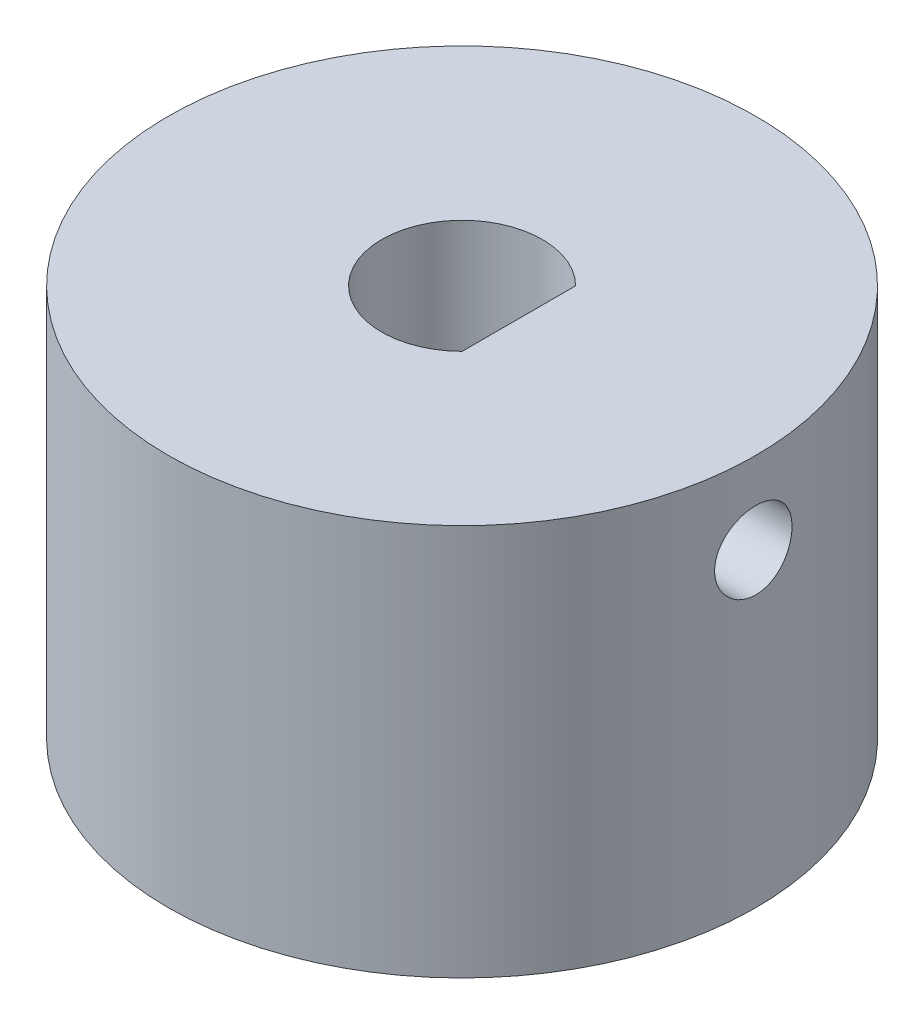
SolidWorks part; units mm, degrees
ref_plane "Front Plane" through (0, 0, 0) normal (0, 0, 1) x (1, 0, 0)
ref_plane "Top Plane" through (0, 0, 0) normal (0, 1, 0) x (1, 0, 0)
ref_plane "Right Plane" through (0, 0, 0) normal (1, 0, 0) x (0, 0, -1)
sketch "Sketch1" plane through (0, 0, 0) normal (0, 1, 0) x (1, 0, 0)
  circle A0 centre (0, 0) radius 9.525
  dimension "D1" = 19.05
extrude "Boss-Extrude1" add sketch "Sketch1" along normal mid plane 12.7
sketch "Sketch2" plane through (0, 6.35, 0) normal (0, 1, 0) x (1, 0, 0)
  line L0 (-2.6035, 4.0795) -> (-2.6035, -2.9289) construction
  line L1 (1.8415, 1.8404) -> (1.8415, -1.8404)
  arc A0 (1.8415, 1.8404) -> (1.8415, -1.8404) centre (0, 0) ccw
  dimension "D2" = 5.207
  dimension "D1" = 4.445
extrude "Cut-Extrude1" cut sketch "Sketch2" against normal up to surface (6.35 mm away) up to plane "Top Plane"
sketch "Sketch3" plane through (0, -6.35, 0) normal (0, -1, 0) x (1, 0, 0)
  line L0 (-4.05, 3.4938) -> (-4.05, -2.4089) construction
  line L1 (2.45, 3.2249) -> (2.45, -3.2249)
  arc A0 (2.45, 3.2249) -> (2.45, -3.2249) centre (0, 0) ccw
  dimension "D1" = 8.1
  dimension "D2" = 6.5
extrude "Cut-Extrude2" cut sketch "Sketch3" against normal up to surface (6.35 mm away) up to plane "Top Plane"
sketch "Sketch4" plane through (0, 0, 0) normal (1, 0, 0) x (0, 0, -1)
  circle A0 centre (0, 3.6904) radius 1.2541
  circle A1 centre (0, -3.3892) radius 1.2541
  dimension "D1" = 2.5082
extrude "Cut-Extrude3" cut sketch "Sketch4" against normal through all contours A1
extrude "Cut-Extrude4" cut sketch "Sketch4<3>" along normal through all contours A0
sketch "Sketch4<3>" plane through (0, 0, 0) normal (1, 0, 0) x (0, 0, -1) same geometry as "Sketch4"
equation "\"D1@Sketch3\"=8.1mm"
equation "\"D2@Sketch3\"=6.5mm"
equation "\"D1@Sketch4\"=3/32+0.005"
